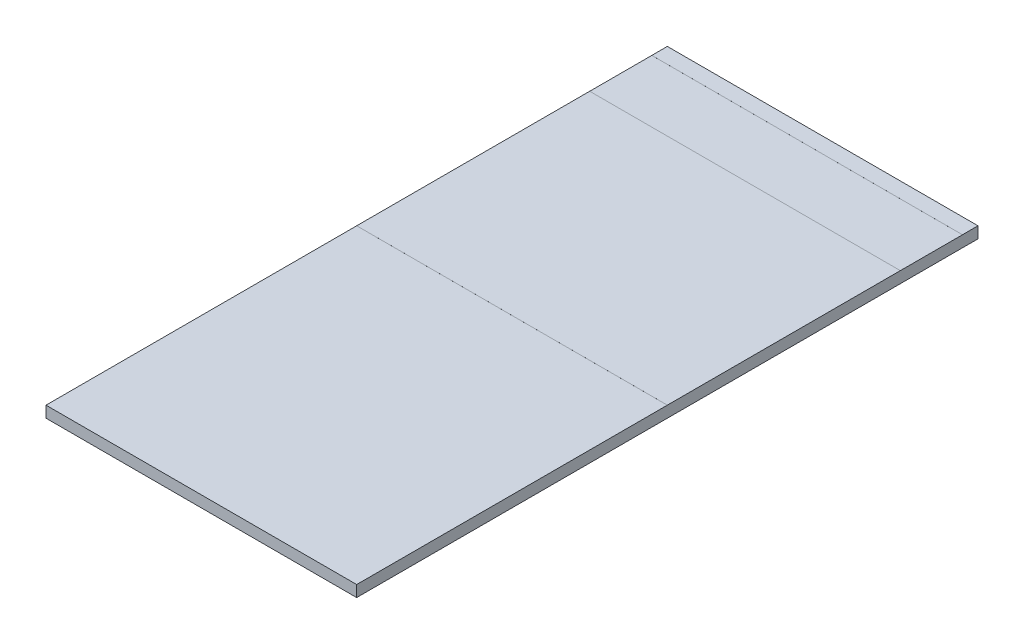
SolidWorks part; units mm, degrees
ref_plane "Top Plane" through (0, 0, 0) normal (0, 0, 1) x (1, 0, 0)
ref_plane "Front Plane" through (0, 0, 0) normal (0, 1, 0) x (1, 0, 0)
ref_plane "Right Plane" through (0, 0, 0) normal (1, 0, 0) x (0, 0, -1)
sketch "Sketch1" plane through (0, 0, 0) normal (0, 0, 1) x (1, 0, 0)
  line L1 (0, 0) -> (2, 0)
  line L2 (0, 0) -> (0, 0.0729)
  line L3 (0, 0.0729) -> (2, 0.0729)
  line L4 (2, 0) -> (2, 0.0729)
  dimension "D1" = 0.0729
  dimension "D2" = 2
extrude "Boss-Extrude1" add sketch "Sketch1" along normal blind 4 contours L3 L4 L1 L2
sketch "Sketch7" plane through (0, 0.0729, 0) normal (0, 1, 0) x (1, 0, 0)
  line L0 (0, -4) -> (0, 0) construction
  line L1 (2, 0) -> (0, 0)
  line L2 (2, 0) -> (2, -0.1)
  line L3 (2, -0.1) -> (0, -0.1)
  line L4 (0, 0) -> (0, -0.1)
  line L5 (2, -4) -> (2, 0) construction
  line L6 (2, -0.5) -> (0, -0.5)
  line L7 (2, -0.5) -> (2, -2)
  line L8 (2, -2) -> (0, -2)
  line L9 (0, -0.5) -> (0, -2)
  point P13 (0, -0.5)
  dimension "D1" = 0.1
  dimension "D2" = 0.5
  dimension "D3" = 2
extrude "Boss-Extrude6" add sketch "Sketch7" along normal blind 0.0001
extrude "Boss-Extrude7" add sketch "Sketch7<2>" against normal blind 0.0001 from vertex starting at point (0, 0, 0)
sketch "Sketch7<2>" plane through (0, 0.0729, 0) normal (0, 1, 0) x (1, 0, 0) same geometry as "Sketch7"
